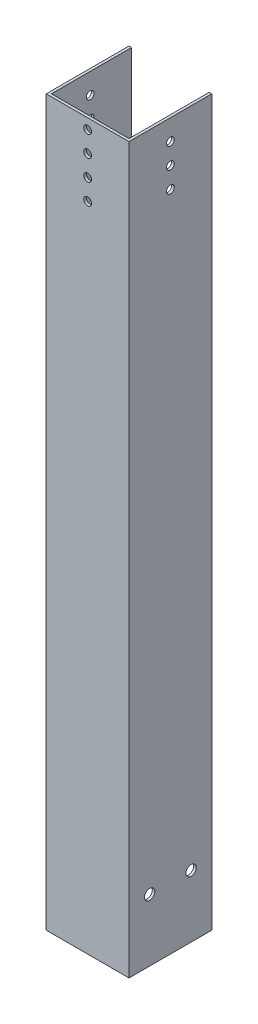
SolidWorks part; units mm, degrees
ref_plane "Front Plane" through (0, 0, 0) normal (0, 0, 1) x (1, 0, 0)
ref_plane "Top Plane" through (0, 0, 0) normal (0, 1, 0) x (1, 0, 0)
ref_plane "Right Plane" through (0, 0, 0) normal (1, 0, 0) x (0, 0, -1)
sketch "Sketch1" plane through (0, 0, 0) normal (0, 1, 0) x (1, 0, 0)
  line L0 (0, 0) -> (50.8, 0)
  line L1 (50.8, 0) -> (50.8, 50.8)
  line L2 (50.8, 50.8) -> (49.2125, 50.8)
  line L3 (49.2125, 50.8) -> (49.2125, 1.5875)
  line L4 (49.2125, 1.5875) -> (1.5875, 1.5875)
  line L5 (1.5875, 1.5875) -> (1.5875, 50.8)
  line L6 (1.5875, 50.8) -> (0, 50.8)
  line L7 (0, 50.8) -> (0, 0)
  dimension "D1" = 50.8
  dimension "D2" = 50.8
  dimension "D3" = 1.5875
  dimension "D4" = 1.5875
  dimension "D5" = 1.5875
extrude "Boss-Extrude1" add sketch "Sketch1" along normal blind 444.5
sketch "Sketch2" plane through (50.8, 0, 0) normal (1, 0, 0) x (0, 0, -1)
  line L0 (0, 444.5) -> (0, 0) construction
  line L1 (0, 0) -> (50.8, 0) construction
  line L3 (0, 444.5) -> (50.8, 444.5) construction
  line L4 (50.8, 444.5) -> (50.8, 0) construction
  circle A0 centre (12.7, 38.1) radius 3.175
  circle A1 centre (38.1, 38.1) radius 3.175
  circle A2 centre (25.4, 406.4) radius 2.3813
  circle A3 centre (25.4, 419.1) radius 2.3813
  circle A4 centre (25.4, 431.8) radius 2.3813
  point P14 (0, 0)
  point P15 (25.4, 493.1212)
  point P16 (25.3756, 453.2922)
  point P17 (26.3738, 478.1129)
  dimension "D1" = 6.35
  dimension "D2" = 25.4
  dimension "D3" = 12.7
  dimension "D4" = 38.1
  dimension "D5" = 4.7625
  dimension "D6" = 12.7
  dimension "D7" = 12.7
  dimension "D8" = 0
  dimension "D9" = 25.4
  dimension "D10" = 0
  dimension "D11" = 12.7
extrude "Cut-Extrude1" cut sketch "Sketch2" against normal through all
sketch "Sketch3" plane through (0, 0, 0) normal (0, 0, 1) x (1, 0, 0)
  line L3 (0, 444.5) -> (0, 0) construction
  line L5 (0, 444.5) -> (50.8, 444.5) construction
  circle A0 centre (25.4, 438.15) radius 2.3813
  circle A1 centre (25.4, 425.45) radius 2.3813
  circle A2 centre (25.4, 412.75) radius 2.3813
  circle A3 centre (25.4, 400.05) radius 2.3813
  dimension "D1" = 4.7625
  dimension "D2" = 25.4
  dimension "D3" = 6.35
  dimension "D4" = 4.7625
  dimension "D5" = 4.7625
  dimension "D6" = 4.7625
  dimension "D7" = 19.05
  dimension "D8" = 31.75
  dimension "D9" = 44.45
extrude "Cut-Extrude2" cut sketch "Sketch3" against normal through all
